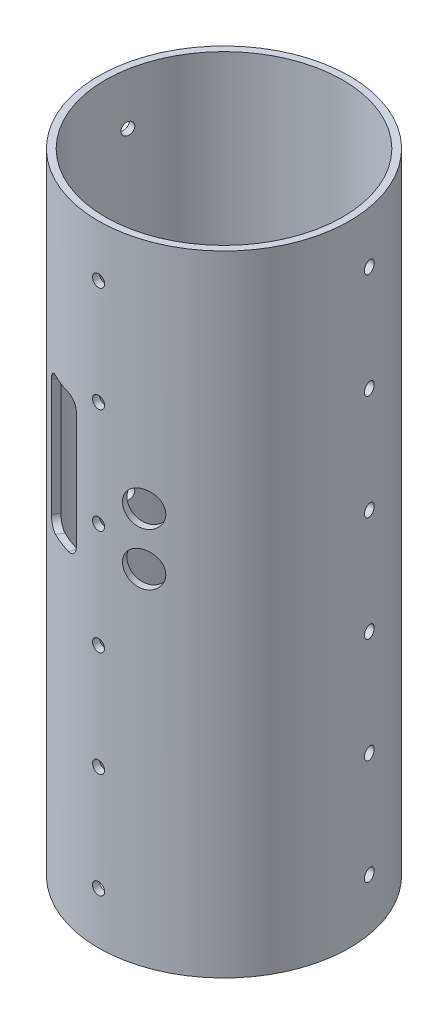
SolidWorks part; units mm, degrees
ref_plane "Front Plane" through (0, 0, 0) normal (0, 0, 1) x (1, 0, 0)
ref_plane "Top Plane" through (0, 0, 0) normal (0, 1, 0) x (1, 0, 0)
ref_plane "Right Plane" through (0, 0, 0) normal (1, 0, 0) x (0, 0, -1)
ref_plane "BULK LENGTH LIMIT" through (0, 183, 0) normal (0, 1, 0) x (1, 0, 0)
ref_axis "ROCKET AXIS" through (0, 146.5, 0) along (0, -1, 0)
sketch "Sketch1" plane through (0, 0, 0) normal (0, 1, 0) x (1, 0, 0)
  circle A0 centre (0, 0) radius 34.5
  circle A1 centre (0, 0) radius 36.5
  dimension "D1" = 69
  dimension "D2" = 2
extrude "BULK" add sketch "Sketch1" along normal up to surface (183 mm away) up to plane "BULK LENGTH LIMIT"
sketch "Sketch2" plane through (0, 0, 0) normal (0, 0, 1) x (1, 0, 0)
  line L0 (40.15, 183) -> (-40.15, 183) construction
  circle A0 centre (0, 15) radius 1.75
  circle A1 centre (0, 45.6) radius 1.75
  circle A2 centre (0, 76.2) radius 1.75
  circle A3 centre (0, 106.8) radius 1.75
  circle A4 centre (0, 137.4) radius 1.75
  circle A5 centre (0, 168) radius 1.75
  dimension "D2" = 3.5
  dimension "D1" = 15
  dimension "D4" = 15
  dimension "D3" = 6
extrude "FRONT HOLE CUTOUTS" cut sketch "Sketch2" along normal through all
pattern_circular "RIGHT HOLE CUTOUTS" count 2 every 100 about axis through (0, 146.5, 0) along (0, -1, 0) of "FRONT HOLE CUTOUTS"
mirror "LEFT HOLE CUTOUTS" about plane through (0, 0, 0) normal (1, 0, 0) of "RIGHT HOLE CUTOUTS"
ref_plane "UMBILICAL CUTOUT START PLANE" through (0, 0, 0) normal (0.9808, 0, 0.1951) x (0, -1, 0)
sketch "Sketch3" plane through (0, 0, 0) normal (0.9808, 0, 0.1951) x (0, -1, 0)
  line L0 (-146.5, 0) -> (-36.5, 0) construction
  line L1 (-94.02, -50) -> (-134.02, -50)
  line L2 (-94.02, -50) -> (-94.02, 0)
  line L3 (-94.02, 0) -> (-134.02, 0)
  line L4 (-134.02, -50) -> (-134.02, 0)
  ellipse E0 centre (-106.8, 0) end of major axis (-108.55, 0) minor radius 0.3414 construction
  dimension "D1" = 40
  dimension "D2" = 50
  dimension "D3" = 12.78
revolve "UMBILICAL CUT" cut sketch "Sketch3" angle 20 about axis through (0, 146.5, 0) along (0, -1, 0)
ref_plane "RBF MIDPLANE" through (0, 0, 0) normal (0.9511, 0, -0.309) x (0, -1, 0)
ref_plane "RBF TANGENT PLANE" through (11.2791, 0, 34.7136) normal (0.309, 0, 0.9511) x (0.9511, 0, -0.309)
sketch "Sketch4" plane through (11.2791, 0, 34.7136) normal (0.309, 0, 0.9511) x (0.9511, 0, -0.309)
  line L0 (0, -60.5) -> (0, 60.5) construction
  circle A0 centre (0, 115.3) radius 5
  circle A1 centre (0, 100.1) radius 5
  dimension "D2" = 10
  dimension "D1" = 15.2
  dimension "D3" = 52.7
extrude "RBF CUTOUTS" cut sketch "Sketch4" against normal up to next
fillet "Fillet1" radius 3 4 edges at (-6.9257, 134.02, 34.8179) (-18.4165, 134.02, 30.3494) (-6.9257, 94.02, 34.8179) (-18.4165, 94.02, 30.3494)
